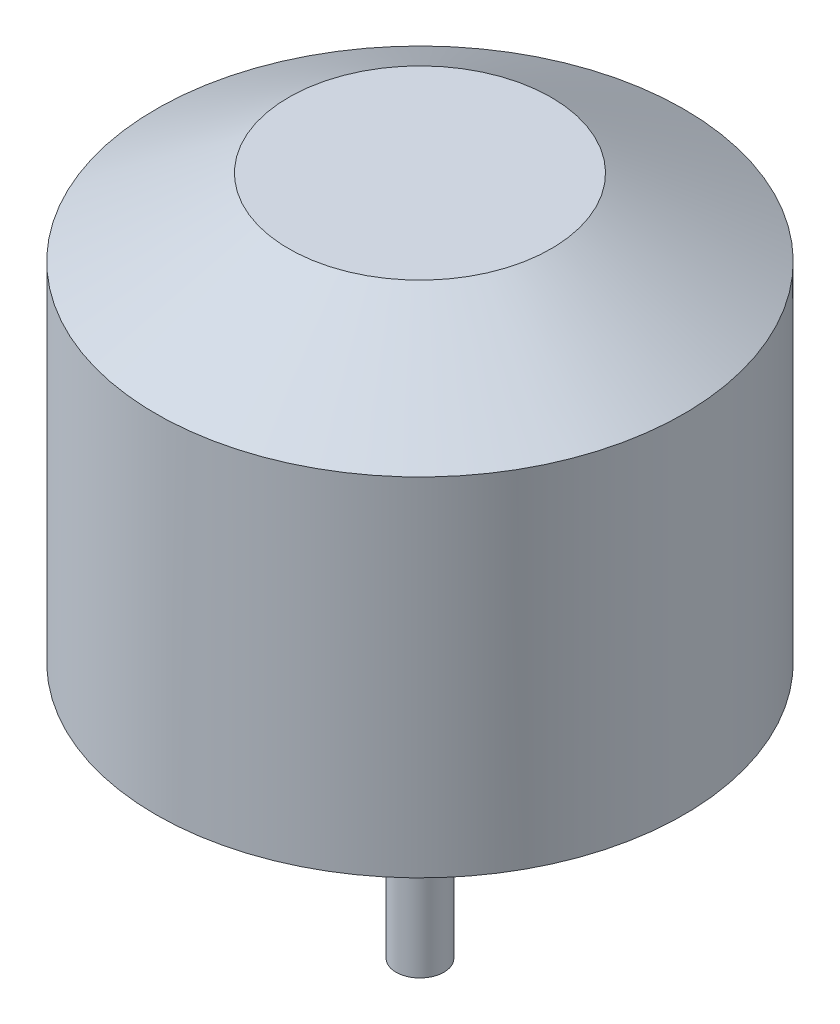
SolidWorks part; units mm, degrees
ref_plane "Front Plane" through (0, 0, 0) normal (0, 0, 1) x (1, 0, 0)
ref_plane "Top Plane" through (0, 0, 0) normal (0, 1, 0) x (1, 0, 0)
ref_plane "Right Plane" through (0, 0, 0) normal (1, 0, 0) x (0, 0, -1)
other "Bounding Box"
ref_plane "Default Plane" through (-8.9266, -12.7485, 0) normal (-0.1736, 0.9848, 0) x (0.9848, 0.1736, 0)
sketch "Sketch1" plane through (0, 0, 0) normal (0, 1, 0) x (1, 0, 0)
  circle A0 centre (0, 0) radius 17.5
  dimension "D1" = 35
extrude "Boss-Extrude1" add sketch "Sketch1" along normal mid plane 28.1
chamfer "Chamfer1" distance 5.08 angle 60 1 edges at (0, 14.05, 17.5) first distance on face at (0, 14.05, 17.5)
sketch "Sketch2" plane through (0, -14.05, 0) normal (0, -1, 0) x (1, 0, 0)
  circle A0 centre (0, 0) radius 1.5875
  dimension "D1" = 3.175
extrude "Boss-Extrude2" add sketch "Sketch2" along normal offset from surface (17 mm away) 45.1 up to face at (0, 14.05, 8.7012)
